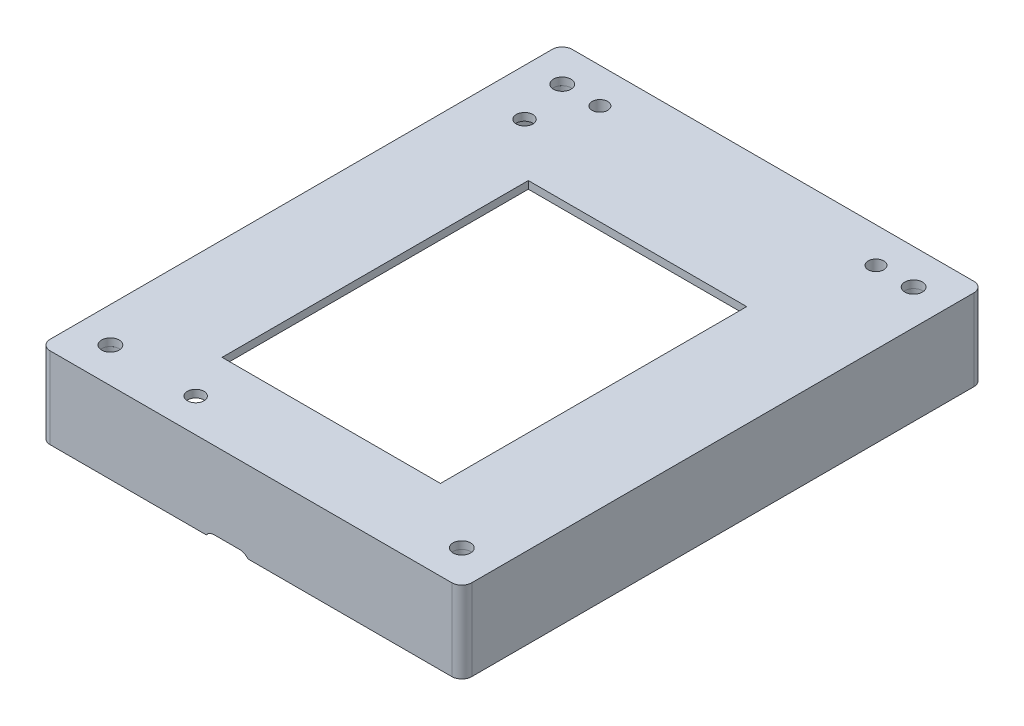
SolidWorks part; units mm, degrees
ref_plane "前视基准面" through (0, 0, 0) normal (0, 0, 1) x (1, 0, 0)
ref_plane "上视基准面" through (0, 0, 0) normal (0, 1, 0) x (1, 0, 0)
ref_plane "右视基准面" through (0, 0, 0) normal (1, 0, 0) x (0, 0, -1)
other "Configuration Table"
sketch "草图1" plane through (0, 0, 0) normal (0, 1, 0) x (1, 0, 0)
  line L1 (-40.5, 50.5) -> (40.5, 50.5)
  line L2 (-40.5, 50.5) -> (-40.5, -50.5)
  line L3 (-40.5, -50.5) -> (40.5, -50.5)
  line L4 (40.5, 50.5) -> (40.5, -50.5)
  line L5 (-40.5, 50.5) -> (40.5, -50.5) construction
  line L6 (-40.5, -50.5) -> (40.5, 50.5) construction
  line L7 (-40, 52) -> (40, 52)
  line L8 (-42, 50) -> (-42, -50)
  line L9 (-40, -52) -> (40, -52)
  line L10 (42, 50) -> (42, -50)
  line L11 (-42, 52) -> (42, -52) construction
  line L12 (-42, -52) -> (42, 52) construction
  arc A0 (-40, 52) -> (-42, 50) centre (-40, 50) ccw
  arc A2 (-42, -50) -> (-40, -52) centre (-40, -50) ccw
  arc A3 (40, -52) -> (42, -50) centre (40, -50) ccw
  arc A4 (42, 50) -> (40, 52) centre (40, 50) ccw
  point P0 (0, 0)
  point P6 (0, 0)
  dimension "D5" = 4
  dimension "D7" = 4
  dimension "D8" = 4
  dimension "D1" = 81
  dimension "D2" = 84
  dimension "D3" = 101
  dimension "D4" = 104
extrude "凸台-拉伸1" add sketch "草图1" along normal blind 16.2
sketch "草图2" plane through (0, 16.2, 0) normal (0, 1, 0) x (1, 0, 0)
  line L0 (40.5, 50.5) -> (-40.5, 50.5) construction
  line L1 (40.5, 50.5) -> (-40.5, 50.5)
  line L2 (-40.5, -50.5) -> (40.5, -50.5) construction
  line L3 (40.5, -50.5) -> (40.5, 50.5) construction
  line L4 (-40.5, 50.5) -> (-40.5, -50.5) construction
  line L5 (-40.5, -50.5) -> (40.5, -50.5)
  line L6 (40.5, -50.5) -> (40.5, 50.5)
  line L7 (-40.5, 50.5) -> (-40.5, -50.5)
extrude "凸台-拉伸2" add sketch "草图2" against normal blind 1.5
sketch "草图3" plane through (0, 16.2, 0) normal (0, 1, 0) x (1, 0, 0)
  line L0 (-40, -52) -> (40, -52) construction
  line L1 (21.75, -36) -> (-21.75, -36)
  line L2 (21.75, -36) -> (21.75, 25)
  line L3 (21.75, 25) -> (-21.75, 25)
  line L4 (-21.75, -36) -> (-21.75, 25)
  line L5 (21.75, -36) -> (-21.75, 25) construction
  line L6 (21.75, 25) -> (-21.75, -36) construction
  line L7 (42, -50) -> (42, 50) construction
  line L11 (40, 52) -> (-40, 52) construction
  line L12 (-42, 50) -> (-42, -50) construction
  circle A0 centre (-32.7, 35.2) radius 1.65
  circle A1 centre (-17.7, -45.3) radius 1.65
  point P0 (0, -5.5)
  dimension "D7" = 3.3
  dimension "D14" = 3.3
  dimension "D1" = 43.5
  dimension "D2" = 16
  dimension "D3" = 20.25
  dimension "D4" = 61
  dimension "D5" = 16.8
  dimension "D6" = 9.3
  dimension "D12" = 24.3
  dimension "D13" = 6.7
extrude "切除-拉伸1" cut sketch "草图3" against normal blind 1.5
sketch "草图4" plane through (0, 16.2, 0) normal (0, 1, 0) x (1, 0, 0)
  line L0 (-42, 50) -> (-42, -50) construction
  line L1 (42, -50) -> (42, 50) construction
  line L2 (-40, -52) -> (40, -52) construction
  line L4 (40, 52) -> (-40, 52) construction
  circle A0 centre (35, 45) radius 1.75
  circle A1 centre (-35, 45) radius 1.75
  circle A2 centre (-35, -45) radius 1.75
  circle A3 centre (35, -45) radius 1.75
  dimension "D3" = 7
  dimension "D4" = 7
  dimension "D5" = 3.5
  dimension "D6" = 3.5
  dimension "D7" = 3.5
  dimension "D8" = 3.5
  dimension "D1" = 7
  dimension "D2" = 7
extrude "切除-拉伸2" cut sketch "草图4" against normal blind 1.5
sketch "草图5" plane through (0, 0, 52) normal (0, 0, 1) x (1, 0, 0)
  line L0 (-7.31, -1.2) -> (-2.21, -1.2) construction
  line L1 (-7.31, 0.8) -> (-2.21, 0.8)
  line L2 (-7.31, -3.2) -> (-2.21, -3.2)
  line L3 (-40, 0) -> (40, 0) construction
  line L5 (-42, 16.2) -> (-42, 0) construction
  arc A0 (-7.31, 0.8) -> (-7.31, -3.2) centre (-7.31, -1.2) ccw
  arc A1 (-2.21, -3.2) -> (-2.21, 0.8) centre (-2.21, -1.2) ccw
  point P2 (-4.76, -1.2)
  dimension "D1" = 2
  dimension "D3" = 34.69
  dimension "D2" = 3.2
  dimension "D4" = 39.79
extrude "切除-拉伸3" cut sketch "草图5" against normal blind 1.5
sketch "草图6" plane through (0, 14.7, 0) normal (0, -1, 0) x (1, 0, 0)
  circle A0 centre (35, -45) radius 1.75 construction
  circle A1 centre (-35, -45) radius 1.75 construction
  circle A2 centre (-35, 45) radius 1.75 construction
  circle A3 centre (35, 45) radius 1.75 construction
  circle A4 centre (35, -45) radius 1.75
  circle A5 centre (-35, -45) radius 1.75
  circle A6 centre (-35, 45) radius 1.75
  circle A7 centre (35, 45) radius 1.75
  circle A8 centre (-35, 45) radius 2.25
  circle A9 centre (35, 45) radius 2.25
  circle A10 centre (-35, -45) radius 2.25
  circle A11 centre (35, -45) radius 2.25
  dimension "D1" = 4.5
  dimension "D2" = 4.5
  dimension "D3" = 4.5
  dimension "D4" = 4.5
extrude "凸台-拉伸3" add sketch "草图6" along normal offset from surface (13.1 mm away) 1.6 separate body up to face at (-1.19, 0, 12.8125)
sketch "草图7" plane through (0, 0, -52) normal (0, 0, -1) x (-1, 0, 0)
  line L0 (42, 16.2) -> (42, 0) construction
  line L1 (10, 7.5) -> (23, 7.5)
  line L2 (10, 7.5) -> (10, 1.5)
  line L3 (10, 1.5) -> (23, 1.5)
  line L4 (23, 7.5) -> (23, 1.5)
  line L5 (-40, 0) -> (40, 0) construction
  dimension "D1" = 19
  dimension "D2" = 13
  dimension "D3" = 6
  dimension "D4" = 1.5
extrude "切除-拉伸4" cut sketch "草图7" against normal up to next (1.5 mm away)
sketch "草图8" plane through (0, 16.2, 0) normal (0, 1, 0) x (1, 0, 0)
  circle A0 centre (-27.5, 45) radius 1.55
  circle A1 centre (27.5, 45) radius 1.55
  circle A2 centre (35, 45) radius 1.75 construction
  point P4 (0, 0)
  point P9 (0, 0)
  point P10 (0, 0)
  dimension "D1" = 3.1
  dimension "D2" = 3.1
  dimension "D3" = 55
  dimension "D4" = 27.5
extrude "切除-拉伸5" cut sketch "草图8" against normal through all
sketch "草图9" plane through (0, 14.7, 0) normal (0, -1, 0) x (1, 0, 0)
  circle A0 centre (27.5, -45) radius 1.55 construction
  circle A1 centre (-27.5, -45) radius 1.55 construction
  circle A2 centre (27.5, -45) radius 1.55
  circle A3 centre (-27.5, -45) radius 1.55
  circle A4 centre (-27.5, -45) radius 2.3588
  circle A5 centre (27.5, -45) radius 2.5232
extrude "凸台-拉伸4" add sketch "草图9" along normal blind 5
sketch "草图10" plane through (0, 9.7, 0) normal (0, -1, 0) x (1, 0, 0)
  circle A0 centre (-27.5, -45) radius 2.3588 construction
  circle A1 centre (27.5, -45) radius 2.5232
  circle A2 centre (27.5, -45) radius 2.5232
  circle A3 centre (-27.5, -45) radius 2.3588
  dimension "D1" = 0
extrude "凸台-拉伸5" add sketch "草图10" along normal blind 1.5
